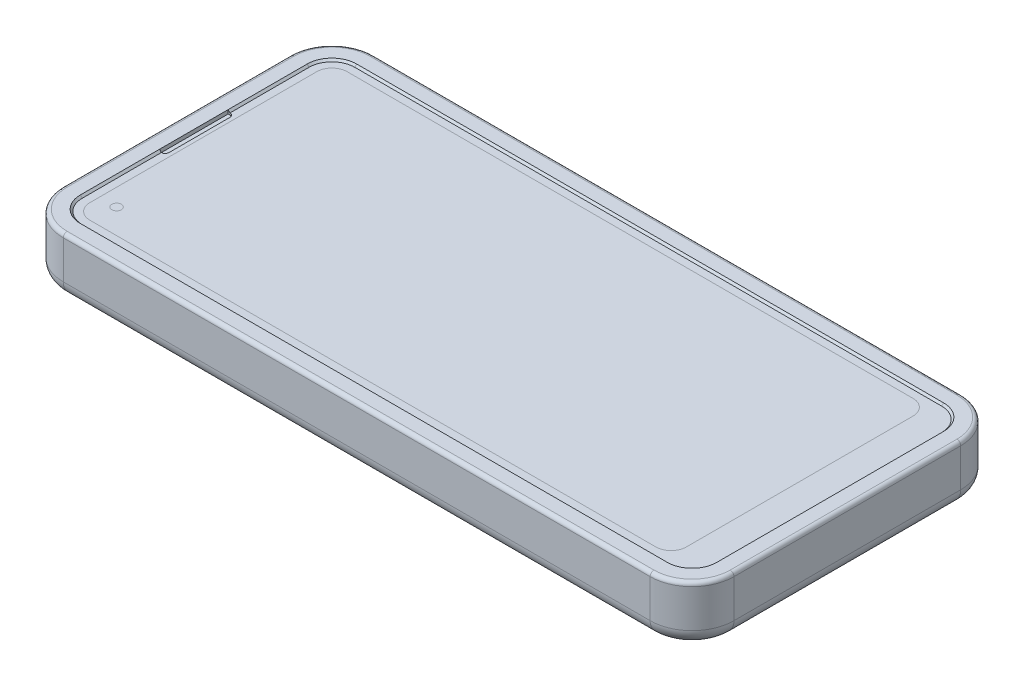
SolidWorks part; units mm, degrees
ref_plane "Alzado" through (0, 0, 0) normal (0, 0, 1) x (1, 0, 0)
ref_plane "Planta" through (0, 0, 0) normal (0, 1, 0) x (1, 0, 0)
ref_plane "Vista lateral" through (0, 0, 0) normal (1, 0, 0) x (0, 0, -1)
sketch "Croquis1" plane through (0, 0, 0) normal (0, 1, 0) x (1, 0, 0)
  line L1 (-77, 40.75) -> (77, 40.75)
  line L2 (-88, 29.75) -> (-88, -29.75)
  line L3 (-77, -40.75) -> (77, -40.75)
  line L4 (88, 29.75) -> (88, -29.75)
  line L5 (-88, 40.75) -> (88, -40.75) construction
  line L6 (-88, -40.75) -> (88, 40.75) construction
  arc A0 (-88, -29.75) -> (-77, -40.75) centre (-77, -29.75) ccw
  arc A1 (77, -40.75) -> (88, -29.75) centre (77, -29.75) ccw
  arc A2 (77, 40.75) -> (88, 29.75) centre (77, 29.75) cw
  arc A3 (-77, 40.75) -> (-88, 29.75) centre (-77, 29.75) ccw
  point P0 (0, 0)
  dimension "D3" = 11
  dimension "D1" = 81.5
  dimension "D2" = 176
extrude "Saliente-Extruir2" add sketch "Croquis1" along normal blind 15
fillet "Redondeo1" radius 1 8 edges at (-84.7782, 15, -37.5282) (0, 15, -40.75) (84.7782, 15, -37.5282) (88, 15, 0) (84.7782, 15, 37.5282) (0, 15, 40.75) (-84.7782, 15, 37.5282) (-88, 15, 0)
fillet "Redondeo2" radius 4 8 edges at (-84.7782, 0, 37.5282) (-88, 0, 0) (-84.7782, 0, -37.5282) (0, 0, -40.75) (84.7782, 0, -37.5282) (88, 0, 0) (84.7782, 0, 37.5282) (0, 0, 40.75)
sketch "Croquis2" plane through (0, 15, 0) normal (0, 1, 0) x (1, 0, 0)
  line L8 (77, 35.75) -> (-77, 35.75)
  line L9 (-83, 29.75) -> (-83, -29.75)
  line L10 (-77, -35.75) -> (77, -35.75)
  line L11 (83, -29.75) -> (83, 29.75)
  line L12 (77, 35.75) -> (-77, 35.75)
  line L13 (-83, 29.75) -> (-83, -29.75)
  line L14 (-77, -35.75) -> (77, -35.75)
  line L15 (83, -29.75) -> (83, 29.75)
  arc A8 (-77, 35.75) -> (-83, 29.75) centre (-77, 29.75) ccw
  arc A9 (-83, -29.75) -> (-77, -35.75) centre (-77, -29.75) ccw
  arc A10 (77, -35.75) -> (83, -29.75) centre (77, -29.75) ccw
  arc A11 (83, 29.75) -> (77, 35.75) centre (77, 29.75) ccw
  arc A12 (-77, 35.75) -> (-83, 29.75) centre (-77, 29.75) ccw
  arc A13 (-83, -29.75) -> (-77, -35.75) centre (-77, -29.75) ccw
  arc A14 (77, -35.75) -> (83, -29.75) centre (77, -29.75) ccw
  arc A15 (83, 29.75) -> (77, 35.75) centre (77, 29.75) ccw
  dimension "D1" = 4
extrude "Cortar-Extruir1" cut sketch "Croquis2" against normal blind 0.5
chamfer "Chaflán1" distance 0.5 angle 45 8 edges at (83, 15, 0) (81.2426, 15, -33.9926) (81.2426, 15, 33.9926) (0, 15, -35.75) (0, 15, 35.75) (-81.2426, 15, -33.9926) (-81.2426, 15, 33.9926) (-83, 15, 0)
sketch "Croquis3" plane through (0, 14.5, 0) normal (0, 1, 0) x (1, 0, 0)
  line L8 (77, 33.75) -> (-77, 33.75)
  line L9 (-81, 29.75) -> (-81, -29.75)
  line L10 (-77, -33.75) -> (77, -33.75)
  line L11 (81, -29.75) -> (81, 29.75)
  line L12 (71.5, 33.75) -> (-77, 33.75)
  line L13 (-81, 29.75) -> (-81, -29.75)
  line L14 (-77, -33.75) -> (71.5, -33.75)
  line L16 (75.5, -29.75) -> (75.5, 29.75)
  line L17 (75.5, -29.75) -> (75.5, 29.75)
  arc A0 (75.5, 29.75) -> (71.5, 33.75) centre (71.5, 29.75) ccw
  arc A8 (81, 29.75) -> (77, 33.75) centre (77, 29.75) ccw
  arc A9 (-77, 33.75) -> (-81, 29.75) centre (-77, 29.75) ccw
  arc A10 (-81, -29.75) -> (-77, -33.75) centre (-77, -29.75) ccw
  arc A11 (77, -33.75) -> (81, -29.75) centre (77, -29.75) ccw
  arc A13 (-77, 33.75) -> (-81, 29.75) centre (-77, 29.75) ccw
  arc A14 (-81, -29.75) -> (-77, -33.75) centre (-77, -29.75) ccw
  arc A16 (75.5, -29.75) -> (71.5, -33.75) centre (71.5, -29.75) cw
  dimension "D1" = 2
  dimension "D2" = 7.5
split line "Línea de partición1"
sketch "Croquis4" plane through (0, 14.5, 0) normal (0, 1, 0) x (1, 0, 0)
  line L0 (71.5, -33.75) -> (-77, -33.75) construction
  line L1 (-81, -29.75) -> (-81, 29.75) construction
  circle A0 centre (-76.5, -27.25) radius 1.25
  dimension "D1" = 2.5
  dimension "D2" = 6.5
  dimension "D3" = 4.5
split line "Línea de partición2"
sketch "Croquis5" plane through (0, 14.5, 0) normal (0, 1, 0) x (1, 0, 0)
  line L1 (-83.5, 9) -> (-83, 9)
  line L2 (-83.5, 9) -> (-83.5, -9)
  line L3 (-83.5, -9) -> (-83, -9)
  line L4 (-82, 8) -> (-82, -8)
  line L5 (-83.5, -29.75) -> (-83.5, 29.75) construction
  arc A0 (-83, -9) -> (-82, -8) centre (-83, -8) ccw
  arc A1 (-83, 9) -> (-82, 8) centre (-83, 8) cw
  point P6 (-82, 0)
  dimension "D3" = 1
  dimension "D1" = 18
  dimension "D2" = 1.5
extrude "Cortar-Extruir2" cut sketch "Croquis5" against normal blind 0.5 and the other way through all
sketch "Croquis6" plane through (0, 0, 0) normal (0, -1, 0) x (1, 0, 0)
  line L0 (-88, -29.75) -> (-88, 29.75) construction
  line L1 (77, -40.75) -> (-77, -40.75) construction
  line L2 (-73.5, -4.75) -> (-57.5, -4.75)
  line L3 (-79.5, -10.75) -> (-79.5, -26.75)
  line L4 (-73.5, -32.75) -> (-57.5, -32.75)
  line L5 (-51.5, -10.75) -> (-51.5, -26.75)
  line L6 (-79.5, -4.75) -> (-51.5, -32.75) construction
  line L7 (-79.5, -32.75) -> (-51.5, -4.75) construction
  circle A0 centre (-42, 0) radius 8
  arc A1 (-79.5, -26.75) -> (-73.5, -32.75) centre (-73.5, -26.75) ccw
  arc A2 (-57.5, -32.75) -> (-51.5, -26.75) centre (-57.5, -26.75) ccw
  arc A3 (-57.5, -4.75) -> (-51.5, -10.75) centre (-57.5, -10.75) cw
  arc A4 (-73.5, -4.75) -> (-79.5, -10.75) centre (-73.5, -10.75) ccw
  point P2 (-65.5, -18.75)
  dimension "D1" = 16
  dimension "D6" = 6
  dimension "D2" = 46
  dimension "D3" = 28
  dimension "D4" = 22.5
  dimension "D5" = 22
extrude "Cortar-Extruir3" cut sketch "Croquis6" against normal blind 3.5
chamfer "Chaflán2" distance 2 angle 60 9 edges at (-79.5, 3.5, -18.75) (-77.7426, 3.5, -6.5074) (-65.5, 3.5, -4.75) (-53.2574, 3.5, -6.5074) (-51.5, 3.5, -18.75) (-53.2574, 3.5, -30.9926) (-65.5, 3.5, -32.75) (-77.7426, 3.5, -30.9926) (-42, 0, -8) first distance on face at (-79.5, 1.75, -18.75) first distance on face at (-77.1213, 1.75, -7.1287) first distance on face at (-65.5, 1.75, -4.75) first distance on face at (-53.8787, 1.75, -7.1287) first distance on face at (-51.5, 1.75, -18.75) first distance on face at (-53.8787, 1.75, -30.3713) first distance on face at (-65.5, 1.75, -32.75) first distance on face at (-77.1213, 1.75, -30.3713) first distance on face at (-42, 0, -8)
sketch "Croquis7" plane through (0, 3.5, 0) normal (0, -1, 0) x (1, 0, 0)
  line L0 (-76.0359, -18.75) -> (-54.9641, -18.75) construction
  line L1 (-76.0359, -10.75) -> (-76.0359, -26.75) construction
  line L2 (-54.9641, -26.75) -> (-54.9641, -10.75) construction
  line L3 (-65.5, -29.2859) -> (-65.5, -8.2141) construction
  line L4 (-73.5, -29.2859) -> (-57.5, -29.2859) construction
  line L5 (-57.5, -8.2141) -> (-73.5, -8.2141) construction
  circle A0 centre (-70.5, -23.75) radius 3.5
  circle A1 centre (-60.5, -23.75) radius 3.5
  circle A2 centre (-60.5, -13.75) radius 3.5
  circle A3 centre (-70.5, -13.75) radius 3.5
  circle A4 centre (-60.5, -23.75) radius 3
  circle A5 centre (-60.5, -13.75) radius 3
  circle A6 centre (-70.5, -13.75) radius 3
  circle A7 centre (-70.5, -23.75) radius 3
  dimension "D1" = 7
  dimension "D2" = 5
  dimension "D3" = 5
  dimension "D6" = 5
  dimension "D7" = 5
  dimension "D8" = 0.5
  dimension "D4" = 2
  dimension "D5" = 2
extrude "Saliente-Extruir3" add sketch "Croquis7" along normal blind 0.5
fillet "Redondeo5" radius 0.25 9 edges at (-60.5, 3.5, -16.75) (-60.5, 3, -16.75) (-70.5, 3, -27.25) (-70.5, 3, -16.75) (-70.5, 3, -17.25) (-60.5, 3, -17.25) (-60.5, 3.5, -27.25) (-60.5, 3, -26.75) (-70.5, 3, -26.75)
sketch "Croquis8" plane through (0, 3.5, 0) normal (0, -1, 0) x (1, 0, 0)
  line L0 (-50, 0) -> (-34, 0) construction
  line L1 (-48.8511, -2.8099) -> (-38.7983, -5.0331)
  line L2 (-38.7983, -5.0331) -> (-38.7983, -4.4928)
  line L3 (-38.7983, -4.4928) -> (-39.4934, -4.3391)
  line L4 (-48.8511, -2.8099) -> (-40.3435, 0)
  line L5 (-38.7983, 5.0331) -> (-38.7983, 4.4928)
  line L6 (-38.7983, 4.4928) -> (-39.4934, 4.3391)
  line L7 (-48.8511, 2.8099) -> (-38.7983, 5.0331)
  line L8 (-48.8511, 2.8099) -> (-40.3435, 0)
  circle A0 centre (-42, 0) radius 8 construction
  circle A1 centre (-42, 0) radius 8 construction
  arc A2 (-39.4934, -4.3391) -> (-39.0193, 0) centre (-39.0193, -2.1955) cw
  arc A3 (-39.4934, 4.3391) -> (-39.0193, 0) centre (-39.0193, 2.1955) ccw
split line "Línea de partición3"
